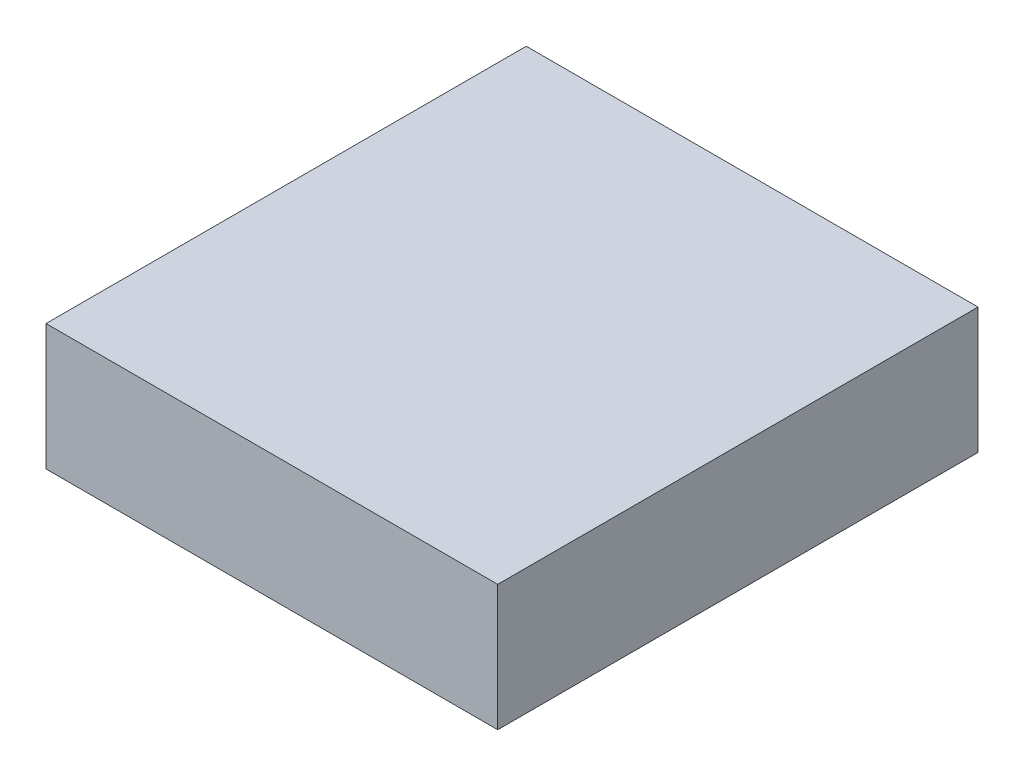
SolidWorks part; units mm, degrees
ref_plane "Front Plane" through (0, 0, 0) normal (0, 0, 1) x (1, 0, 0)
ref_plane "Top Plane" through (0, 0, 0) normal (0, 1, 0) x (1, 0, 0)
ref_plane "Right Plane" through (0, 0, 0) normal (1, 0, 0) x (0, 0, -1)
sketch "Sketch1" plane through (0, 0, 0) normal (0, 1, 0) x (1, 0, 0)
  line L1 (0, 0) -> (107.6, 0)
  line L2 (0, 0) -> (0, 114.4)
  line L3 (0, 114.4) -> (107.6, 114.4)
  line L4 (107.6, 0) -> (107.6, 114.4)
  dimension "D1" = 114.4
  dimension "D2" = 107.6
extrude "Boss-Extrude1" add sketch "Sketch1" along normal blind 30
